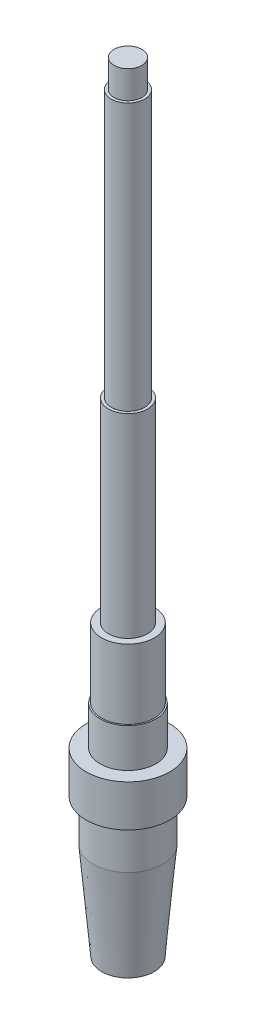
SolidWorks part; units mm, degrees
ref_plane "Płaszczyzna przednia" through (0, 0, 0) normal (0, 0, 1) x (1, 0, 0)
ref_plane "Płaszczyzna górna" through (0, 0, 0) normal (0, 1, 0) x (1, 0, 0)
ref_plane "Płaszczyzna prawa" through (0, 0, 0) normal (1, 0, 0) x (0, 0, -1)
sketch "Szkic1" plane through (0, 0, 0) normal (0, 0, 1) x (1, 0, 0)
  line L0 (0, 140) -> (0, -140) construction
  line L1 (0, -140) -> (9.4379, -140)
  line L2 (9.4379, -140) -> (12.5, -105)
  line L3 (12.5, -105) -> (12.5, -90)
  line L4 (12.5, -90) -> (15, -90)
  line L5 (15, -90) -> (15, -75)
  line L6 (15, -75) -> (10, -75)
  line L7 (10, -75) -> (10, -61)
  line L8 (10, -61) -> (9.5, -61)
  line L9 (9.5, -61) -> (9.5, -36)
  line L10 (9.5, -36) -> (7, -36)
  line L11 (7, -36) -> (7, 34)
  line L12 (7, 34) -> (6, 34)
  line L13 (6, 34) -> (6, 130)
  line L14 (6, 130) -> (5, 130)
  line L15 (5, 130) -> (5, 140)
  line L16 (5, 140) -> (0, 140)
  line L17 (0, 140) -> (0, -140)
  dimension "D1" = 25
  dimension "D2" = 5
  dimension "D3" = 35
  dimension "D4" = 15
  dimension "D5" = 15
  dimension "D6" = 30
  dimension "D7" = 20
  dimension "D8" = 14
  dimension "D9" = 19
  dimension "D10" = 25
  dimension "D11" = 14
  dimension "D12" = 12
  dimension "D13" = 220
  dimension "D14" = 10
  dimension "D15" = 10
  dimension "D16" = 70
revolve "Obrót1" add sketch "Szkic1" angle 360 about L0
ref_plane "Płaszczyzna1" through (0, 0, -12.5) normal (0, 0, -1) x (-1, 0, 0)
sketch "Szkic2" plane through (0, 0, -12.5) normal (0, 0, -1) x (-1, 0, 0)
  line L0 (0, -140) -> (0, -110) construction
  line L1 (-9.4379, -140) -> (9.4379, -140) construction
  line L2 (-3, -140) -> (-3, -110)
  line L3 (3, -140) -> (3, -110)
  arc A0 (-3, -140) -> (3, -140) centre (0, -140) ccw
  arc A1 (3, -110) -> (-3, -110) centre (0, -110) ccw
  point P4 (0, -125)
  dimension "D1" = 6
  dimension "D2" = 30
extrude "Wytnij-wyciągnięcie1" cut sketch "Szkic2" against normal blind 7
ref_plane "Płaszczyzna2" through (0, 0, -7) normal (0, 0, -1) x (-1, 0, 0)
sketch "Szkic3" plane through (0, 0, -7) normal (0, 0, -1) x (-1, 0, 0)
  line L0 (0, 21.5) -> (0, -23.5) construction
  line L1 (2.5, 21.5) -> (2.5, -23.5)
  line L2 (-2.5, 21.5) -> (-2.5, -23.5)
  line L3 (9.5, -36) -> (-9.5, -36) construction
  line L6 (7, 34) -> (-7, 34) construction
  arc A0 (2.5, 21.5) -> (-2.5, 21.5) centre (0, 21.5) ccw
  arc A1 (-2.5, -23.5) -> (2.5, -23.5) centre (0, -23.5) ccw
  point P3 (0, -1)
  point P9 (0, -26)
  point P15 (0, 24)
  dimension "D2" = 10
  dimension "D1" = 5
  dimension "D3" = 10
extrude "Wytnij-wyciągnięcie2" cut sketch "Szkic3" against normal blind 3
hole_wizard "Otwór gwintowany M81" positions "Szkic4" profile "Szkic5" tap size "M8" standard "DIN"
sketch "Szkic4" plane through (0, -140, 0) normal (0, -1, 0) x (-1, 0, 0)
  point P0 (0, 0)
sketch "Szkic5" plane through (0, -140, 0) normal (1, 0, 0) x (0, 0, -1)
  line L0 (0, 0) -> (0, 24.2929)
  line L1 (0, 24.2929) -> (3.4, 22.25)
  line L2 (3.4, 22.25) -> (3.4, 0)
  line L5 (3.4, 0) -> (0, 0)
  line L10 (0, 24.2929) -> (-3.4, 22.25) construction
  line L11 (0, -6.35) -> (0, 107.95) construction
  dimension "Średnica wiertła gwintu" = 6.8
  dimension "Głębokość otworu gwintowanego" = 22.25
  dimension "Kąt wiertła" = 118
cosmetic thread "Gwint otworu1" parameters "D1"=16, "D2"=8
